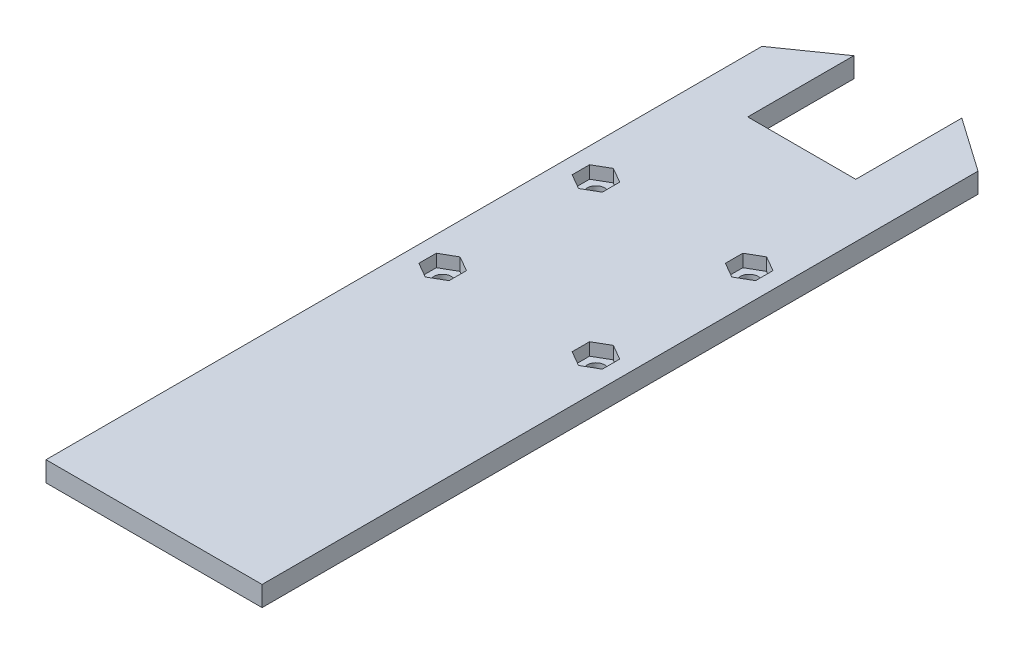
SolidWorks part; units mm, degrees
material "ABS"
ref_plane "Front Plane" through (0, 0, 0) normal (0, 0, 1) x (1, 0, 0)
ref_plane "Top Plane" through (0, 0, 0) normal (0, 1, 0) x (1, 0, 0)
ref_plane "Right Plane" through (0, 0, 0) normal (1, 0, 0) x (0, 0, -1)
sketch "Sketch1" plane through (0, 0, 0) normal (0, 1, 0) x (1, 0, 0)
  line L1 (21.5, -75) -> (-21.5, -75)
  line L2 (21.5, -75) -> (21.5, 75)
  line L3 (21.5, 75) -> (-21.5, 75)
  line L4 (-21.5, -75) -> (-21.5, 75)
  line L5 (21.5, -75) -> (-21.5, 75) construction
  line L6 (21.5, 75) -> (-21.5, -75) construction
  point P0 (0, 0)
  dimension "D1" = 43
  dimension "D2" = 150
extrude "Boss-Extrude1" add sketch "Sketch1" along normal blind 4
sketch "Sketch2" plane through (0, 4, 0) normal (0, 1, 0) x (1, 0, 0)
  line L0 (21.5, 75) -> (0, 75) construction
  line L1 (21.5, 75) -> (-21.5, 75) construction
  line L2 (0, 75) -> (0, 53.9) construction
  line L4 (0, 53.9) -> (10.57, 53.9)
  line L5 (0, 53.9) -> (0, 75)
  line L6 (0, 75) -> (10.57, 75)
  line L7 (10.57, 53.9) -> (10.57, 75)
  line L8 (0, 53.9) -> (-10.75, 53.9)
  line L9 (0, 53.9) -> (0, 75)
  line L10 (0, 75) -> (-10.75, 75)
  line L11 (-10.75, 53.9) -> (-10.75, 75)
  dimension "D1" = 21.5
  dimension "D2" = 21.1
  dimension "D3" = 10.57
  dimension "D4" = 10.75
  dimension "D5" = 21.1
extrude "Cut-Extrude1" cut sketch "Sketch2" against normal through all contours L9 L8 L11 L10 | L5 L4 L7 L6
sketch "Sketch3" plane through (0, 4, 0) normal (0, 1, 0) x (1, 0, 0)
  line L0 (21.5, 75) -> (15.25, 75) construction
  line L1 (21.5, 75) -> (10.57, 75) construction
  line L2 (15.25, 75) -> (15.25, 28.19) construction
  line L3 (0, -2.31) -> (0, 28.19) construction
  line L4 (15.25, 28.19) -> (-15.25, 28.19) construction
  line L5 (15.25, 28.19) -> (15.25, -2.31) construction
  line L6 (15.25, -2.31) -> (-15.25, -2.31) construction
  line L7 (-15.25, 28.19) -> (-15.25, -2.31) construction
  line L8 (-15.25, 31.6541) -> (-18.25, 29.9221)
  line L9 (-18.25, 29.9221) -> (-18.25, 26.4579)
  line L10 (-18.25, 26.4579) -> (-15.25, 24.7259)
  line L11 (-15.25, 24.7259) -> (-12.25, 26.4579)
  line L12 (-12.25, 26.4579) -> (-12.25, 29.9221)
  line L13 (-12.25, 29.9221) -> (-15.25, 31.6541)
  line L14 (-15.25, 12.94) -> (15.25, 12.94) construction
  line L15 (12.25, 29.9221) -> (15.25, 31.6541)
  line L16 (12.25, 26.4579) -> (12.25, 29.9221)
  line L17 (15.25, 24.7259) -> (12.25, 26.4579)
  line L18 (18.25, 26.4579) -> (15.25, 24.7259)
  line L19 (18.25, 29.9221) -> (18.25, 26.4579)
  line L20 (15.25, 31.6541) -> (18.25, 29.9221)
  line L21 (12.25, -0.5779) -> (12.25, -4.0421)
  line L22 (15.25, 1.1541) -> (12.25, -0.5779)
  line L23 (18.25, -0.5779) -> (15.25, 1.1541)
  line L24 (18.25, -4.0421) -> (18.25, -0.5779)
  line L25 (15.25, -5.7741) -> (18.25, -4.0421)
  line L26 (12.25, -4.0421) -> (15.25, -5.7741)
  line L27 (-12.25, -4.0421) -> (-15.25, -5.7741)
  line L28 (-12.25, -0.5779) -> (-12.25, -4.0421)
  line L29 (-15.25, 1.1541) -> (-12.25, -0.5779)
  line L30 (-18.25, -0.5779) -> (-15.25, 1.1541)
  line L31 (-18.25, -4.0421) -> (-18.25, -0.5779)
  line L32 (-15.25, -5.7741) -> (-18.25, -4.0421)
  circle A1 centre (-15.25, 28.19) radius 3 construction
  dimension "D1" = 6.25
  dimension "D2" = 46.81
  dimension "D3" = 30.5
  dimension "D4" = 30.5
  dimension "D5" = 6
extrude "Cut-Extrude2" cut sketch "Sketch3" against normal blind 2.5
sketch "Sketch4" plane through (0, 4, 0) normal (0, 1, 0) x (1, 0, 0)
  line L0 (-18.25, 12.94) -> (18.25, 12.94) construction
  line L1 (-18.25, 29.9221) -> (18.25, 29.9221) construction
  line L2 (-18.25, 29.9221) -> (-18.25, -4.0421) construction
  line L3 (-18.25, -4.0421) -> (18.25, -4.0421) construction
  line L4 (18.25, 29.9221) -> (18.25, -4.0421) construction
  line L5 (0, 29.9221) -> (0, -4.0421) construction
  line L6 (-15.25, 24.7259) -> (-15.25, 31.6541) construction
  circle A0 centre (-15.25, 28.19) radius 1.75
  circle A1 centre (15.25, 28.19) radius 1.75
  circle A2 centre (15.25, -2.31) radius 1.75
  circle A3 centre (-15.25, -2.31) radius 1.75
  dimension "D1" = 3.5
extrude "Cut-Extrude3" cut sketch "Sketch4" against normal through all
sketch "Sketch6" plane through (0, 4, 0) normal (0, 1, 0) x (1, 0, 0)
  line L0 (21.5, 75) -> (10.75, 75) construction
  line L1 (21.5, 75) -> (10.57, 75) construction
  line L2 (-21.5, 75) -> (-10.75, 75)
  line L4 (10.75, 75) -> (10.57, 75)
  line L5 (10.75, 75) -> (10.75, 53.9)
  line L6 (10.75, 53.9) -> (10.57, 53.9)
  line L7 (10.57, 75) -> (10.57, 53.9)
  dimension "D1" = 10.75
extrude "Cut-Extrude5" cut sketch "Sketch6" against normal through all contours L5 L4 L7 L6
sketch "Sketch5" plane through (0, 4, 0) normal (0, 1, 0) x (1, 0, 0)
  line L4 (0, 53.9) -> (0, 75) construction
  line L5 (10.75, 53.9) -> (-10.75, 53.9) construction
  line L9 (-10.75, 75) -> (-21.5, 75)
  line L10 (-10.75, 75) -> (-21.5, 67.4728)
  line L11 (-21.5, 75) -> (-21.5, -75) construction
  line L12 (-21.5, 67.4728) -> (-21.5, 75)
  line L13 (10.75, 75) -> (21.5, 75)
  line L14 (10.75, 75) -> (21.5, 67.4728)
  line L15 (21.5, 67.4728) -> (21.5, 75)
  dimension "D1" = 35
extrude "Cut-Extrude6" cut sketch "Sketch5" against normal through all
